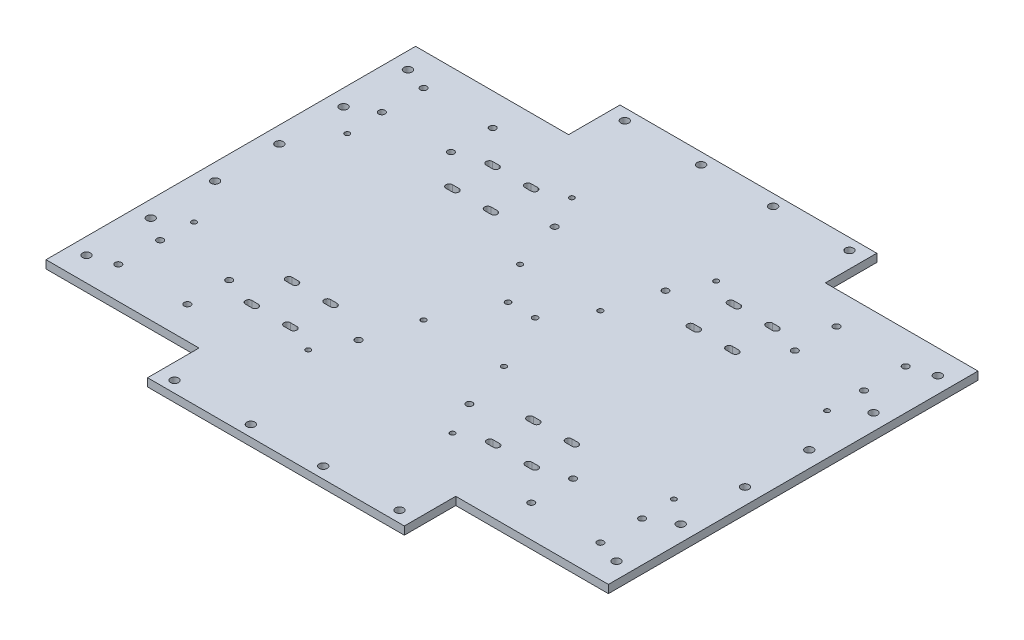
SolidWorks part; units mm, degrees
ref_plane "Front Plane" through (0, 0, 0) normal (0, 0, 1) x (1, 0, 0)
ref_plane "Top Plane" through (0, 0, 0) normal (0, 1, 0) x (1, 0, 0)
ref_plane "Right Plane" through (0, 0, 0) normal (1, 0, 0) x (0, 0, -1)
sketch "Sketch1" plane through (0, 0, 0) normal (0, 1, 0) x (1, 0, 0)
  line L2 (-175, 115) -> (-175, -115)
  line L4 (175, 115) -> (175, -115)
  line L8 (-79.7939, 147) -> (80, 147)
  line L12 (-79.7939, -147) -> (80, -147)
  line L18 (-79.7939, 147) -> (-79.7939, 115)
  line L19 (-79.7939, 115) -> (-175, 115)
  line L20 (-79.7939, -147) -> (-79.7939, -115)
  line L21 (-79.7939, -115) -> (-175, -115)
  line L22 (80, 147) -> (80, 115)
  line L23 (80, 115) -> (175, 115)
  line L24 (80, -147) -> (80, -115)
  line L25 (80, -115) -> (175, -115)
  line L26 (-79.7939, -115) -> (80, -115) construction
  line L29 (-79.7939, 115) -> (80, -115) construction
  line L30 (80, 115) -> (-79.7939, -115) construction
  line L31 (-79.7939, 115) -> (80, 115) construction
  circle A0 centre (-150, 95) radius 2
  circle A1 centre (-107, 95) radius 2
  circle A2 centre (-150, 69) radius 2
  circle A3 centre (-107, 69) radius 2
  circle A4 centre (-107, -95) radius 2
  circle A5 centre (-150, -95) radius 2
  circle A6 centre (-150, -69) radius 2
  circle A7 centre (-107, -69) radius 2
  circle A8 centre (107, -69) radius 2
  circle A9 centre (150, -69) radius 2
  circle A10 centre (150, -95) radius 2
  circle A11 centre (107, -95) radius 2
  circle A12 centre (107, 69) radius 2
  circle A13 centre (150, 69) radius 2
  circle A14 centre (107, 95) radius 2
  circle A15 centre (150, 95) radius 2
  dimension "D9" = 4
  dimension "D19" = 230
  dimension "D3" = 32
  dimension "D4" = 32
  dimension "D7" = 43
  dimension "D8" = 26
  dimension "D10" = 20
  dimension "D12" = 43
  dimension "D13" = 26
  dimension "D14" = 43
  dimension "D15" = 26
  dimension "D16" = 43
  dimension "D17" = 26
  dimension "D20" = 25
  dimension "D21" = 20
  dimension "D22" = 25
  dimension "D23" = 25
  dimension "D24" = 350
extrude "Boss-Extrude1" add sketch "Sketch1" along normal blind 5
sketch "Sketch2" plane through (0, 5, 0) normal (0, 1, 0) x (1, 0, 0)
  line L1 (175, 115) -> (80, 115) construction
  circle A0 centre (-69.7939, 140) radius 2.5
  circle A1 centre (-22.2939, 140) radius 2.5
  circle A2 centre (22.5, 140) radius 2.5
  circle A3 centre (70, 140) radius 2.5
  circle A11 centre (165, 100) radius 2.5
  circle A18 centre (70, -140) radius 2.5
  circle A19 centre (22.5, -140) radius 2.5
  circle A20 centre (-22.5, -140) radius 2.5
  circle A21 centre (-70, -140) radius 2.5
  circle A22 centre (165, 60) radius 2.5
  circle A23 centre (165, 20) radius 2.5
  circle A24 centre (165, -20) radius 2.5
  circle A25 centre (165, -60) radius 2.5
  circle A26 centre (165, -100) radius 2.5
  circle A27 centre (-164.7939, -100) radius 2.5
  circle A28 centre (-164.7939, -60) radius 2.5
  circle A29 centre (-164.7939, -20) radius 2.5
  circle A30 centre (-164.7939, 20) radius 2.5
  circle A31 centre (-164.7939, 60) radius 2.5
  circle A32 centre (-164.7939, 100) radius 2.5
  dimension "D1" = 6
  dimension "D2" = 15
  dimension "D5" = 47.5
  dimension "D6" = 47.5
extrude "Cut-Extrude2" cut sketch "Sketch2" against normal blind 5 contours A30 | A31 | A32 | A0 | A28 | A1 | A2 | A3 | A11 | A18 | A19 | A20 | A21 | A22 | A29 | A27 | A23 | A24 | A25 | A26 region at (-69.7939, 5, -140) region at (-164.7939, 5, -20) region at (-164.7939, 5, -60) region at (-164.7939, 5, -100)
sketch "Sketch3" plane through (0, 5, 0) normal (0, 1, 0) x (1, 0, 0)
  line L0 (0.1031, 147) -> (0.1031, -147) construction
  line L1 (80, 147) -> (-79.7939, 147) construction
  line L2 (-79.7939, -147) -> (80, -147) construction
  line L3 (0.1031, -147) -> (-175, 0) construction
  line L4 (-175, 115) -> (-175, -115) construction
  line L5 (-175, 0) -> (175, 0) construction
  line L6 (175, -115) -> (175, 115) construction
  line L7 (-85, 51.9064) -> (-89, 51.9064)
  line L8 (61.2061, 51.9064) -> (65.2061, 51.9064)
  line L9 (-89, 47.9064) -> (-85, 47.9064)
  line L10 (-61, 51.9064) -> (-65, 51.9064)
  line L11 (-61, 47.9064) -> (-65, 47.9064)
  line L12 (-61, 76.9064) -> (-65, 76.9064)
  line L13 (-61, 72.9064) -> (-65, 72.9064)
  line L14 (-85, 76.9064) -> (-89, 76.9064)
  line L15 (-85, 72.9064) -> (-89, 72.9064)
  line L16 (65.2061, 47.9064) -> (61.2061, 47.9064)
  line L17 (85.2061, 51.9064) -> (89.2061, 51.9064)
  line L18 (89.2061, 47.9064) -> (85.2061, 47.9064)
  line L19 (85.2061, 76.9064) -> (89.2061, 76.9064)
  line L20 (65.2061, 76.9064) -> (61.2061, 76.9064)
  line L21 (89.2061, 72.9064) -> (85.2061, 72.9064)
  line L22 (65.2061, -72.9064) -> (61.2061, -72.9064)
  line L23 (65.2061, 72.9064) -> (61.2061, 72.9064)
  line L24 (89.2061, -72.9064) -> (85.2061, -72.9064)
  line L25 (65.2061, -76.9064) -> (61.2061, -76.9064)
  line L26 (85.2061, -76.9064) -> (89.2061, -76.9064)
  line L27 (89.2061, -47.9064) -> (85.2061, -47.9064)
  line L28 (85.2061, -51.9064) -> (89.2061, -51.9064)
  line L29 (65.2061, -47.9064) -> (61.2061, -47.9064)
  line L30 (-85, -72.9064) -> (-89, -72.9064)
  line L31 (-85, -76.9064) -> (-89, -76.9064)
  line L32 (-61, -72.9064) -> (-65, -72.9064)
  line L33 (-61, -76.9064) -> (-65, -76.9064)
  line L34 (-61, -47.9064) -> (-65, -47.9064)
  line L35 (-61, -51.9064) -> (-65, -51.9064)
  line L36 (-89, -47.9064) -> (-85, -47.9064)
  line L37 (61.2061, -51.9064) -> (65.2061, -51.9064)
  line L38 (-85, -51.9064) -> (-89, -51.9064)
  arc A8 (-85, 72.9064) -> (-85, 76.9064) centre (-85, 74.9064) ccw
  arc A9 (-89, 76.9064) -> (-89, 72.9064) centre (-89, 74.9064) ccw
  arc A10 (-65, 76.9064) -> (-65, 72.9064) centre (-65, 74.9064) ccw
  arc A11 (-61, 72.9064) -> (-61, 76.9064) centre (-61, 74.9064) ccw
  arc A12 (-89, 51.9064) -> (-89, 47.9064) centre (-89, 49.9064) ccw
  arc A13 (-85, 47.9064) -> (-85, 51.9064) centre (-85, 49.9064) ccw
  arc A14 (-65, 51.9064) -> (-65, 47.9064) centre (-65, 49.9064) ccw
  arc A15 (-61, 47.9064) -> (-61, 51.9064) centre (-61, 49.9064) ccw
  arc A17 (61.2061, 76.9064) -> (61.2061, 72.9064) centre (61.2061, 74.9064) ccw
  arc A18 (65.2061, 72.9064) -> (65.2061, 76.9064) centre (65.2061, 74.9064) ccw
  arc A19 (85.2061, 76.9064) -> (85.2061, 72.9064) centre (85.2061, 74.9064) ccw
  arc A21 (61.2061, 51.9064) -> (61.2061, 47.9064) centre (61.2061, 49.9064) ccw
  arc A22 (65.2061, 47.9064) -> (65.2061, 51.9064) centre (65.2061, 49.9064) ccw
  arc A23 (85.2061, 51.9064) -> (85.2061, 47.9064) centre (85.2061, 49.9064) ccw
  arc A24 (89.2061, 47.9064) -> (89.2061, 51.9064) centre (89.2061, 49.9064) ccw
  arc A25 (89.2061, 72.9064) -> (89.2061, 76.9064) centre (89.2061, 74.9064) ccw
  arc A26 (89.2061, -72.9064) -> (89.2061, -76.9064) centre (89.2061, -74.9064) cw
  arc A27 (89.2061, -47.9064) -> (89.2061, -51.9064) centre (89.2061, -49.9064) cw
  arc A28 (85.2061, -51.9064) -> (85.2061, -47.9064) centre (85.2061, -49.9064) cw
  arc A29 (65.2061, -47.9064) -> (65.2061, -51.9064) centre (65.2061, -49.9064) cw
  arc A30 (61.2061, -51.9064) -> (61.2061, -47.9064) centre (61.2061, -49.9064) cw
  arc A31 (85.2061, -76.9064) -> (85.2061, -72.9064) centre (85.2061, -74.9064) cw
  arc A32 (65.2061, -72.9064) -> (65.2061, -76.9064) centre (65.2061, -74.9064) cw
  arc A33 (61.2061, -76.9064) -> (61.2061, -72.9064) centre (61.2061, -74.9064) cw
  arc A34 (-61, -47.9064) -> (-61, -51.9064) centre (-61, -49.9064) cw
  arc A35 (-65, -51.9064) -> (-65, -47.9064) centre (-65, -49.9064) cw
  arc A36 (-85, -47.9064) -> (-85, -51.9064) centre (-85, -49.9064) cw
  arc A37 (-89, -51.9064) -> (-89, -47.9064) centre (-89, -49.9064) cw
  arc A38 (-61, -72.9064) -> (-61, -76.9064) centre (-61, -74.9064) cw
  arc A39 (-65, -76.9064) -> (-65, -72.9064) centre (-65, -74.9064) cw
  arc A40 (-89, -76.9064) -> (-89, -72.9064) centre (-89, -74.9064) cw
  arc A41 (-85, -72.9064) -> (-85, -76.9064) centre (-85, -74.9064) cw
extrude "Cut-Extrude3" cut sketch "Sketch3" against normal blind 10
sketch "Sketch4" plane through (0, 5, 0) normal (0, 1, 0) x (1, 0, 0)
  line L8 (0.1031, 147) -> (0.1031, -147) construction
  line L9 (80, 147) -> (-79.7939, 147) construction
  line L10 (-79.7939, -147) -> (80, -147) construction
  line L11 (175, 0) -> (-175, 0) construction
  line L12 (175, -115) -> (175, 115) construction
  line L13 (-175, 115) -> (-175, -115) construction
  line L14 (10.853, 0) -> (-10.6469, 0) construction
  line L15 (0.1031, 8.2227) -> (0.1031, -8.2227) construction
  circle A3 centre (8.503, 5.894) radius 1.7
  circle A4 centre (-8.2969, 5.8513) radius 1.7
  point P21 (0.1031, 0)
  point P26 (0.1031, 0)
extrude "Cut-Extrude4" cut sketch "Sketch4" against normal blind 10
sketch "Sketch5" plane through (0, 5, 0) normal (0, 1, 0) x (1, 0, 0)
  line L2 (-79.7939, -147) -> (80, -147) construction
  line L3 (80, 147) -> (-79.7939, 147) construction
  circle A0 centre (-149.206, 46.6552) radius 1.55
  circle A1 centre (-149.206, -48.7153) radius 1.55
  circle A2 centre (-44.8185, -82) radius 1.55
  circle A3 centre (-44.7766, 82) radius 1.55
  circle A4 centre (44.9827, 82) radius 1.55
  circle A5 centre (149.4122, 46.6552) radius 1.55
  circle A6 centre (149.4122, -48.7153) radius 1.55
  circle A7 centre (44.9827, -82) radius 1.55
  point P28 (0, 0)
  dimension "D1" = 65
  dimension "D2" = 65
  dimension "D3" = 65
  dimension "D4" = 65
extrude "Cut-Extrude5" cut sketch "Sketch5" against normal blind 10
sketch "Sketch6" plane through (0, 5, 0) normal (0, 1, 0) x (1, 0, 0)
  circle A0 centre (-34.4727, 61.0381) radius 2
  circle A1 centre (34.4727, 61.0381) radius 2
  circle A2 centre (34.4727, -61.0381) radius 2
  circle A3 centre (-34.4727, -61.0381) radius 2
extrude "Cut-Extrude6" cut sketch "Sketch6" against normal blind 15
sketch "Sketch7" plane through (0, 5, 0) normal (0, 1, 0) x (1, 0, 0)
  line L0 (-25, 0) -> (25, 0) construction
  circle A0 centre (-25, 30) radius 1.6
  circle A1 centre (25, 30) radius 1.6
  circle A2 centre (25, -30) radius 1.6
  circle A3 centre (-25, -30) radius 1.6
  dimension "D1" = 50
  dimension "D2" = 60
extrude "Cut-Extrude7" cut sketch "Sketch7" against normal blind 10
